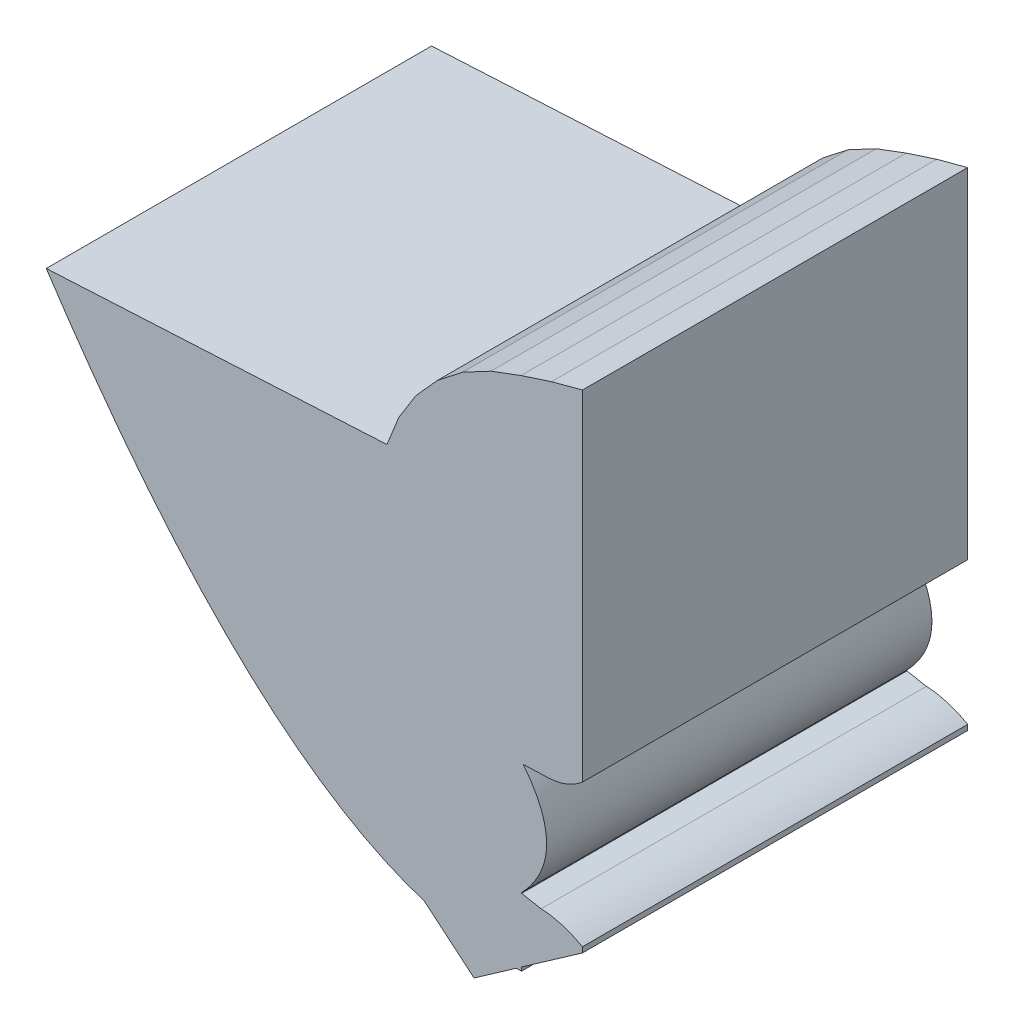
SolidWorks part; units mm, degrees
ref_plane "Alzado" through (0, 0, 0) normal (0, 0, 1) x (1, 0, 0)
ref_plane "Planta" through (0, 0, 0) normal (0, 1, 0) x (1, 0, 0)
ref_plane "Vista lateral" through (0, 0, 0) normal (1, 0, 0) x (0, 0, -1)
sketch "Croquis1" plane through (0, 0, 0) normal (0, 0, 1) x (1, 0, 0)
  line L0 (-8.9818, 12.6082) -> (-23.0359, 11.8716) construction
  line L1 (-8.9818, 12.6082) -> (-23.0359, 11.8716)
  line L2 (-8.9818, 12.6082) -> (-23.0359, 11.8716) construction
  line L3 (-2.1773, 6.1864) -> (-2.1773, -4.6845)
  line L4 (-8.9818, 12.6082) -> (-23.0359, 11.8716)
  line L6 (-1.3949, 1.9763) -> (0.3551, 2.2848) construction
  line L7 (-1.3949, 1.9763) -> (0.3551, 2.2848) construction
  line L8 (0.3551, 2.2848) -> (0.3551, 2.8423) construction
  line L9 (0.3551, 2.2848) -> (0.3551, 3.0015) construction
  line L10 (0.3551, -2.2848) -> (-1.3949, -2.2237) construction
  line L11 (0.3551, -2.2848) -> (-1.3949, -2.2237) construction
  line L12 (0.3551, 2.2848) -> (0.3551, -2.2848) construction
  line L13 (0.3551, -2.2848) -> (0.3551, -2.7233) construction
  line L14 (-8.9818, 12.6082) -> (-6.9949, 10.4774)
  line L15 (-23.0359, 11.5401) -> (-23.0359, 11.8716) construction
  line L16 (-23.0359, 11.5401) -> (-23.0359, 11.8716)
  arc A0 (-18.9452, 7.5409) -> (-23.0359, 11.5401) centre (-69.8841, -40.4718) ccw construction
  arc A1 (-18.9452, 7.5409) -> (-23.0359, 11.5401) centre (-69.8841, -40.4718) ccw
  spline S1 degree 2 poles (-4119.0151, 24659.0515) (3413.1083, -24757.661) (-2705.4818, 24835.5983) knots 0.405517 0.405517 0.405517 0.594449 0.594449 0.594449 weights 1 1 1 only from (-18.9452, 7.5409) to (-2.8466, -5.0591) construction
  spline S2 degree 2 poles (-18.9452, 7.5409) (-10.215, -3.6976) (-2.8466, -5.0591) knots 0.497667 0.497667 0.497667 0.499554 0.499554 0.499554 weights 1 1 1
  spline S3 degree 2 poles (-23607.9882, 8212.1168) (23492.4763, -8550.6979) (-23372.6553, 8887.1675) knots 0.40552 0.40552 0.40552 0.594498 0.594498 0.594498 weights 1 1 1 only from (0.3551, 3.0015) to (-6.9949, 10.4774) construction
  spline S4 degree 2 poles (-2.1773, 6.1864) (-4.0633, 8.1416) (-6.9949, 10.4774) knots 0.501383 0.501383 0.501383 0.502013 0.502013 0.502013 weights 1 1 1
  spline S5 degree 2 poles (-1.3949, -2.2237) (-0.9075, -0.1237) (-1.3949, 1.9763) knots 0 0 0 1 1 1 weights 1 3.231801 1 construction
  spline S6 degree 2 poles (-1.3949, -2.2237) (-0.9075, -0.1237) (-1.3949, 1.9763) knots 0 0 0 1 1 1 weights 1 3.231801 1 construction
  spline S7 degree 2 poles (-24934.0908, 1769.912) (24899.5391, -2178.5787) (-24858.838, 2586.1022) knots 0.405518 0.405518 0.405518 0.594474 0.594474 0.594474 weights 1 1 1 only from (-2.8466, -5.0591) to (0.3551, -2.7233) construction
  spline S8 degree 2 poles (-2.8466, -5.0591) (-2.4982, -4.873) (-2.1773, -4.6845) knots 0.498812 0.498812 0.498812 0.498912 0.498912 0.498912 weights 1 1 1
extrude "croquis base" add sketch "Croquis1" along normal mid plane 14.42 contours S2 S8 L13 L11 S6 L7 L9 S4 L14 L1 L16 A1 region at (-10.1535, 5.1597, 0)
sketch "Croquis6" plane through (0, 0, 0) normal (1, 0, 0) x (0, 0, -1)
  line L0 (7.21, 12.6082) -> (7.21, 10.4774) construction
  line L1 (7.21, 12.6082) -> (7.21, -5.0591)
  line L2 (-7.21, 12.6082) -> (-7.21, 10.4774) construction
  line L3 (-7.21, 12.6082) -> (-7.21, -5.0591)
  line L4 (-7.21, -5.0591) -> (7.21, -5.0591) construction
  line L5 (-7.21, -5.0591) -> (-5.21, -5.0591)
  line L6 (7.21, 12.6082) -> (5.21, -5.0591)
  line L7 (-7.21, 12.6082) -> (-5.21, -5.0591)
  line L8 (5.21, -5.0591) -> (7.21, -5.0591)
  dimension "D1" = 2
  dimension "D2" = 2
sketch "Croquis9" plane through (0, 0, 0) normal (0, 0, 1) x (1, 0, 0)
  line L0 (0, 0) -> (-4.9559, 0) construction
  line L1 (-2.4454, 0.1046) -> (-1.25, 0) construction
  line L2 (-1.25, 0) -> (-1.25, -4.2203) construction
  line L3 (-2.1773, -1.8404) -> (-2.1773, -4.3883)
  line L4 (-2.1773, 6.1864) -> (-2.1773, -4.6845) construction
  line L5 (-2.4454, 0.1046) -> (-2.0532, -4.3783) construction
  line L6 (-2.4454, 0.1046) -> (-15.184, 3.0892) construction
  line L7 (-19.6099, 15.4015) -> (-15.184, 3.0892) construction
  line L9 (-15.184, 3.0892) -> (-25.9078, 12.6462) construction
  line L10 (-15.184, 3.0892) -> (-13.3572, 5.139) construction
  line L11 (-19.9694, 9.4938) -> (-10.3098, 10)
  line L12 (-10.3098, 10) -> (-2.1773, 6.0829)
  line L13 (-2.1773, 6.0829) -> (-2.1773, 2.4242)
  line L15 (-2.1773, 6.1864) -> (-2.1773, -4.6845) construction
  parabola Q0 (-2.1773, 2.4242) -> (-2.1773, -1.8404) focus (-2.4454, 0.1046) apex (-1.25, 0)
  parabola Q1 (-2.1773, -4.3883) -> (-19.9694, 9.4938) focus (-2.4454, 0.1046) apex (-2.0532, -4.3783)
  spline S0 degree 2 poles (-18.9452, 7.5409) (-10.215, -3.6976) (-2.8466, -5.0591) knots 0.497667 0.497667 0.497667 0.499554 0.499554 0.499554 weights 1 1 1 construction
  dimension "D1" = 95
  dimension "D2" = 1.25
  dimension "D3" = 1.2
  dimension "D4" = 4.5
  dimension "D5" = 5
  dimension "D6" = 3
  dimension "D7" = 10
extrude "lente ppal 1" add sketch "Croquis9" along normal up to surface and the other way up to surface contours Q1 L3 Q0 L13 L12 L11 region at (-9.1064, 3.5992, 0) up to face at (-11.7662, 6.8113, 7.21) other way up to face at (-11.7662, 6.8113, -7.21)
extrude "lente ppal 2" cut sketch "Croquis9<3>" against normal through all both and the other way through all flip side to cut
sketch "Croquis9<3>" plane through (0, 0, 0) normal (0, 0, 1) x (1, 0, 0) same geometry as "Croquis9"
sketch "Croquis8" plane through (0, 0, 0) normal (0, 0, 1) x (1, 0, 0)
  line L0 (-8.9818, 12.6082) -> (-23.0359, 11.8716) construction
  line L1 (-10.3098, 10) -> (0.1, 15.5879) construction
  line L3 (0.1, 2.8777) -> (0.1, 15.5879)
  line L5 (-7.2179, 10.162) -> (-6.7684, 11.2747)
  line L6 (-6.7684, 11.2747) -> (-6.1325, 12.2923)
  line L7 (-6.1325, 12.2923) -> (-5.3295, 13.1841)
  line L8 (-5.3295, 13.1841) -> (-4.3839, 13.9229)
  line L9 (-4.3839, 13.9229) -> (-3.3244, 14.4863)
  line L10 (-3.3244, 14.4863) -> (-2.2004, 14.9065)
  line L11 (-2.2004, 14.9065) -> (-1.0591, 15.2773)
  line L12 (-1.0591, 15.2773) -> (0.1, 15.5879)
  line L13 (-0.5, 2) -> (-9.2621, 13.0152) construction
  line L14 (-9.2621, 13.0152) -> (-9.6721, 13.4466) construction
  line L15 (-9.2621, 13.0152) -> (-9.8313, 13.8617) construction
  line L16 (-0.5, 2) -> (-6.9932, 10.7183) construction
  line L17 (-6.9932, 10.7183) -> (-9.8657, 11.8789) construction
  line L18 (-0.5, 2) -> (-6.4504, 11.7835) construction
  line L19 (-1.1905, 2.3769) -> (-13.6677, 1.9412) construction
  line L20 (-6.4504, 11.7835) -> (-8.5297, 13.0828) construction
  line L21 (-0.5, 2) -> (-5.731, 12.7382) construction
  line L22 (-0.5, 2) -> (-4.8567, 13.5535) construction
  line L23 (-4.8567, 13.5535) -> (-7.2264, 16.5865) construction
  line L24 (-0.5, 2) -> (-3.8542, 14.2046) construction
  line L25 (-3.8542, 14.2046) -> (-5.6175, 17.521) construction
  line L26 (-0.5, 2) -> (-2.7624, 14.6964) construction
  line L27 (-2.7624, 14.6964) -> (-4.1395, 18.3795) construction
  line L28 (-0.5, 2) -> (-1.6297, 15.0919) construction
  line L29 (-1.6297, 15.0919) -> (-2.365, 17.3548) construction
  line L30 (-0.5, 2) -> (-0.4796, 15.4326) construction
  line L31 (-0.4796, 15.4326) -> (-1.0837, 17.6873) construction
  line L32 (-6.4504, 11.7835) -> (-9.194, 13.4978) construction
  line L33 (-5.731, 12.7382) -> (-8.3325, 15.0806) construction
  line L34 (-10.3098, 10) -> (-10.3098, 19.2428) construction
  line L35 (-0.4796, 15.4326) -> (-1.3923, 18.839) construction
  line L36 (-10.3098, 10) -> (-7.2179, 10.162)
  line L37 (-6.9932, 10.7183) -> (-7.7178, 13.8573) construction
  line L38 (-6.9932, 10.7183) -> (-7.6851, 10.9979) construction
  line L39 (-6.4504, 11.7835) -> (-7.328, 15.5847) construction
  line L40 (-6.4504, 11.7835) -> (-8.1247, 12.8297) construction
  line L41 (-5.731, 12.7382) -> (-6.4786, 15.9764) construction
  line L42 (-5.731, 12.7382) -> (-7.1919, 14.0536) construction
  line L43 (-4.8567, 13.5535) -> (-5.8037, 17.6554) construction
  line L44 (-4.8567, 13.5535) -> (-6.0786, 15.1174) construction
  line L45 (-3.8542, 14.2046) -> (-4.8235, 18.4032) construction
  line L46 (-3.8542, 14.2046) -> (-4.9673, 16.2982) construction
  line L47 (-2.7624, 14.6964) -> (-3.6965, 18.7423) construction
  line L48 (-2.7624, 14.6964) -> (-3.4418, 16.5134) construction
  line L49 (-0.5, 2) -> (-0.5437, 2.5) construction
  line L50 (-0.5437, 2.5) -> (-0.8858, 3.4397) construction
  line L51 (0, 0) -> (0, 1.5958) construction
  line L52 (0, 12.6082) -> (0, -5.0591) construction
  line L53 (-1.6297, 15.0919) -> (-2.8173, 18.7468) construction
  line L54 (-1.6297, 15.0919) -> (-2.2911, 17.9567) construction
  line L55 (-0.4796, 15.4326) -> (-1.0428, 17.8722) construction
  line L56 (-10.3098, 10) -> (-2.1773, 2.3425)
  line L57 (-2.1773, 2.3425) -> (-1.1905, 2.3769)
  line L58 (-10.3098, 10) -> (-19.9694, 9.4938) construction
  line L60 (-2.1773, 6.0829) -> (-10.3098, 10) construction
  parabola Q0 (-1.1905, 2.3769) -> (0.1, 2.8777) focus (-0.8858, 3.4397) apex (-0.5437, 2.5)
  spline S1 degree 2 poles (-10.3098, 10) (-2.4445, 4.1882) (-0.2283, 0.4324) knots 0.500548 0.500548 0.500548 0.502013 0.502013 0.502013 weights 1 1 1 construction
  dimension "D1" = 5.039
  dimension "D3" = 15
  dimension "D4" = 25
  dimension "D5" = 80
  dimension "D6" = 45
  dimension "D7" = 35
  dimension "D8" = 7.5
  dimension "D9" = 5
  dimension "D10" = 55
  dimension "D11" = 211.322
  dimension "D12" = 206.691
  dimension "D13" = 202.027
  dimension "D14" = 197.339
  dimension "D15" = 192.633
  dimension "D16" = 0.5
  dimension "D17" = 0.5
  dimension "D18" = 2
  dimension "D19" = 5
  dimension "D20" = 20
  dimension "D21" = 88
  dimension "D22" = 1
  dimension "D23" = 0.1
  dimension "D24" = 178
  dimension "D25" = 1.2
  dimension "D26" = 10
extrude "lente frontal" add sketch "Croquis8" along normal up to surface and the other way up to surface up to face at (-5.0154, 2.8272, 7.21) other way up to face at (-7.9808, 4.4301, -7.21)
sketch "Croquis11" plane through (0, 0, 0) normal (0, 0, 1) x (1, 0, 0)
  line L0 (0, 0) -> (0, -3.4622) construction
  line L1 (0, 0) -> (3.4097, 0) construction
  line L2 (0, 0) -> (-1.5, -2) construction
  line L3 (0.0193, -2.4148) -> (0.0108, -2.901) construction
  line L4 (-1.5262, -3.4998) -> (-1.5, -2) construction
  line L5 (-1.4477, -2.0014) -> (-2.6004, -1.9611) construction
  line L6 (0.0108, -2.901) -> (-0.0904, -2.7858) construction
  line L7 (0.1, -2.4588) -> (0.1, -2.6588)
  line L8 (0.1, 2.8777) -> (0.1, 15.5879) construction
  line L9 (0.0108, -2.901) -> (0.8474, -2.1663) construction
  line L10 (-0.4724, -2.8467) -> (0.0108, -2.901) construction
  line L11 (-1.3889, -2.3589) -> (-0.0204, -2.973) construction
  line L12 (-0.0204, -2.973) -> (-2.5614, -3.2818) construction
  line L13 (-0.0204, -2.973) -> (-1.479, -0.8696) construction
  line L14 (-1.4477, -2.0014) -> (-10.0297, -0.405)
  line L15 (-10.0297, -0.405) -> (-3.9576, -5.5)
  line L16 (-3.9576, -5.5) -> (-3.9576, 4.2291) construction
  line L17 (0.1, -2.6588) -> (-3.9576, -5.5)
  parabola Q0 (-1.4477, -2.0014) -> (0.1, -2.4588) focus (-1.5262, -3.4998) apex (-1.5, -2)
  parabola Q1 (0.1, -2.6588) -> (-3.9576, -5.5) focus (-1.3889, -2.3589) apex (-0.0204, -2.973) construction
  dimension "D1" = 2
  dimension "D2" = 88
  dimension "D3" = 1.5
  dimension "D4" = 1.5
  dimension "D5" = 1
  dimension "D6" = 0.2
  dimension "D7" = 5.5
  dimension "D8" = 1.5
  dimension "D9" = 105
  dimension "D10" = 55
extrude "lente trasera" add sketch "Croquis11" along normal up to surface and the other way up to surface up to face at (-3.7041, 8.4573, 7.21) other way up to face at (-4.8085, 9.1371, -7.21)
